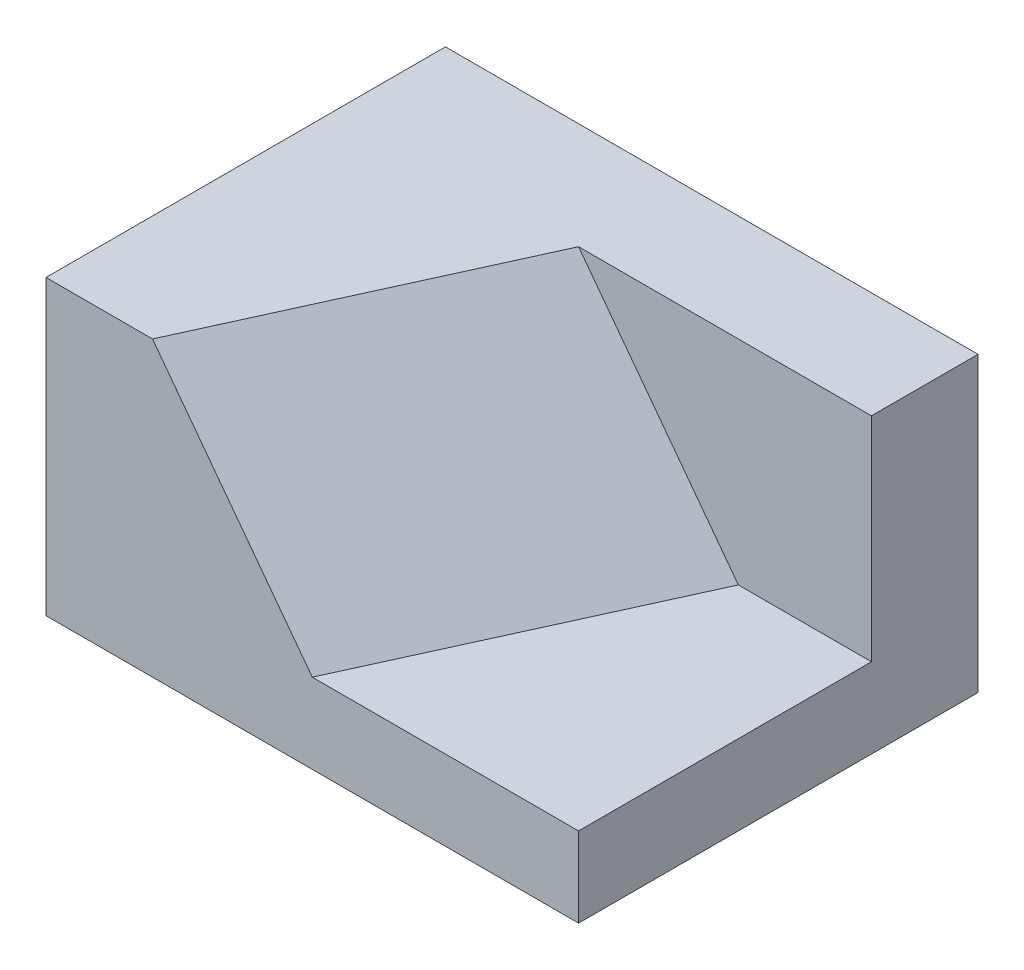
SolidWorks part; units mm, degrees
ref_plane "Front Plane" through (0, 0, 0) normal (0, 0, 1) x (1, 0, 0)
ref_plane "Top Plane" through (0, 0, 0) normal (0, 1, 0) x (1, 0, 0)
ref_plane "Right Plane" through (0, 0, 0) normal (1, 0, 0) x (0, 0, -1)
sketch "Sketch1" plane through (0, 0, 0) normal (1, 0, 0) x (0, 0, -1)
  line L0 (-20, 55) -> (-20, 15)
  line L1 (0, 0) -> (-75, 0)
  line L2 (0, 0) -> (0, 55)
  line L3 (0, 55) -> (-75, 55)
  line L4 (-75, 0) -> (-75, 55)
  line L5 (-20, 15) -> (-75, 15)
  dimension "D1" = 75
  dimension "D2" = 55
  dimension "D3" = 20
  dimension "D4" = 15
extrude "Boss-Extrude1" add sketch "Sketch1" along normal blind 100 contours L0 L5 L4 L1 L2 L3 region at (0, 54.0699, 10)
extrude "Boss-Extrude2" add sketch "Sketch1<3>" along normal blind 75 contours L5 L0 L3 L4 region at (0, 35, 47.5)
sketch "Sketch1<3>" plane through (0, 0, 0) normal (1, 0, 0) x (0, 0, -1) same geometry as "Sketch1"
sketch "Sketch2" plane through (0, 55, 0) normal (0, 1, 0) x (1, 0, 0)
  line L0 (75, -75) -> (0, -75) construction
  line L3 (0, 0) -> (0, -75) construction
  point P0 (45, -20)
  point P1 (20, -75)
  dimension "D1" = 45
  dimension "D2" = 20
sketch "Sketch3" plane through (0, 0, 75) normal (0, 0, 1) x (1, 0, 0)
  line L0 (100, 0) -> (100, 15) construction
  point P0 (50, 15)
  dimension "D1" = 50
ref_plane "Plane1" through (53.892, 40.419, 24.4964) normal (-0.7518, -0.5639, -0.3417) x (-0.2734, -0.205, 0.9398)
sketch "Sketch4" plane through (53.892, 40.419, 24.4964) normal (-0.7518, -0.5639, -0.3417) x (-0.2734, -0.205, 0.9398)
  line L0 (53.7391, 32) -> (-4.7844, 17)
  line L1 (-4.7844, 17) -> (-4.7844, -33)
  line L2 (-4.7844, -33) -> (53.7391, -18)
  line L3 (53.7391, -18) -> (53.7391, 32)
extrude "Cut-Extrude1" cut sketch "Sketch4" along direction (-1, 0, 0) on the side against the normal blind 75
